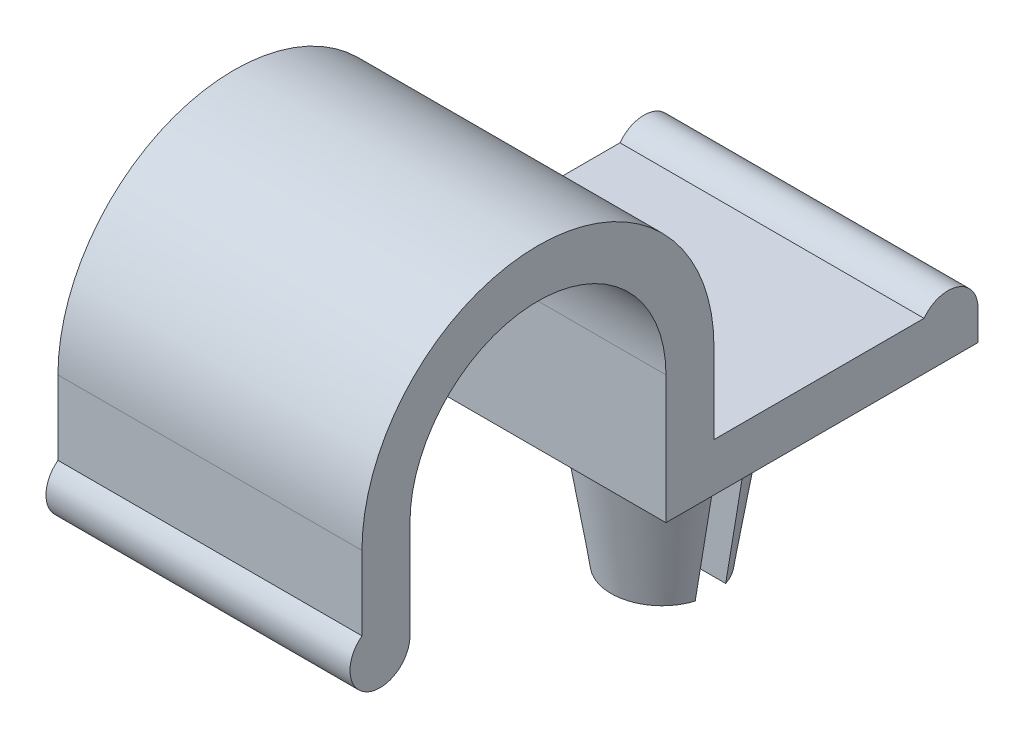
SolidWorks part; units mm, degrees
ref_plane "Front" through (0, 0, 0) normal (0, 0, 1) x (1, 0, 0)
ref_plane "Top" through (0, 0, 0) normal (0, 1, 0) x (1, 0, 0)
ref_plane "Right" through (0, 0, 0) normal (1, 0, 0) x (0, 0, -1)
sketch "Sketch1" plane through (0, 0, 0) normal (-1, 0, 0) x (0, 0, 1)
  line L0 (-9.65, -2) -> (-4.4, -2)
  line L1 (4.4, 0) -> (4.4, -1.85)
  line L2 (3.2, 0) -> (3.2, -2.45)
  line L3 (-3.2, 0) -> (-3.2, -3.2)
  line L4 (-4.4, 0) -> (-4.4, -2)
  line L5 (-6.9, -2) -> (-6.9, -8.7588) construction
  line L6 (-3.2, -3.2) -> (-11, -3.2)
  line L7 (-11, -3.2) -> (-11, -2.45)
  line L8 (-9.65, -2) -> (-9.65, -3.2) construction
  line L9 (3.2, 0) -> (4.4, 0) construction
  arc A0 (3.2, 0) -> (-3.2, 0) centre (0, 0) ccw
  arc A1 (4.4, 0) -> (-4.4, 0) centre (0, 0) ccw
  arc A2 (3.2, -2.45) -> (4.4, -1.85) centre (3.95, -2.45) ccw
  arc A3 (-9.65, -2) -> (-11, -2.45) centre (-10.25, -2.45) ccw
  dimension "D1" = 6.4
  dimension "D2" = 1.2
  dimension "D4" = 0.75
  dimension "D6" = 15.7
  dimension "D3" = 7.6
  dimension "D8" = 6.9
  dimension "D9" = 4.1
extrude "Base-Extrude" add sketch "Sketch1" along normal mid plane 7.6
sketch "Sketch4" plane through (0, 0, 0) normal (-1, 0, 0) x (0, 0, 1)
  line L0 (-6.9, -3.2) -> (-6.9, -7.851)
  line L2 (-6.9, -7.851) -> (-5.63, -7.851)
  line L3 (-6.9, -3.2) -> (-6.9, -2) construction
  line L4 (-5.15, -4.851) -> (-5.4, -4.851)
  line L5 (-5.4, -4.851) -> (-5.4, -3.2)
  line L6 (-5.4, -3.2) -> (-6.9, -3.2)
  line L8 (-5.15, -4.851) -> (-5.63, -7.851)
  line L9 (-11, -3.2) -> (-3.2, -3.2) construction
  dimension "D2" = 3
  dimension "D3" = 1.651
  dimension "D4" = 3
  dimension "D5" = 1.27
  dimension "D6" = 3.5
revolve "Boss-Revolve1" add sketch "Sketch4" angle 360 about L3
sketch "Sketch5" plane through (0, 0, 0) normal (-1, 0, 0) x (0, 0, 1)
  line L0 (-8.17, -7.851) -> (-5.63, -7.851) construction
  line L1 (-7.281, -7.851) -> (-6.519, -7.851)
  line L2 (-7.281, -7.851) -> (-7.281, -3.787)
  line L3 (-6.9, -2) -> (-6.9, -8.7588) construction
  line L4 (-6.519, -7.851) -> (-6.519, -3.787)
  arc A0 (-6.519, -3.787) -> (-7.281, -3.787) centre (-6.9, -3.787) ccw
  dimension "D1" = 0.762
  dimension "D3" = 4.064
extrude "Cut-Extrude1" cut sketch "Sketch5" against normal through all and the other way through all
sketch "Sketch6" plane through (-3.8, 0, 0) normal (-1, 0, 0) x (0, 0, 1)
  point P0 (0, 0)
sketch "Sketch7" plane through (3.8, 0, 0) normal (1, 0, 0) x (0, 0, -1)
  point P0 (0, 0)
ref_axis "Clip Axis" through (-3.8, 0, 0) along (1, 0, 0)
other "RPoint1"
ref_axis "Axis1" through (1.2, 0, 0) along (-1, 0, 0)
other "RPoint2"
ref_axis "Axis2" through (-1.2, 0, 0) along (1, 0, 0)
sketch "FilterSketch" plane through (0, 0, 0) normal (0, 0, 1) x (1, 0, 0)
  circle A0 centre (0, 0) radius 3.2
  circle A1 centre (0, 0) radius 3.2
  circle A2 centre (0, 0) radius 2.35
  dimension "NominalDiameter" = 6.4
  dimension "InnerDiameter" = 4.7
  dimension "OuterDiameter" = 6.4
ref_axis "Axis of Rotation" through (0, -3.2, -6.9) along (0, -1, 0)
